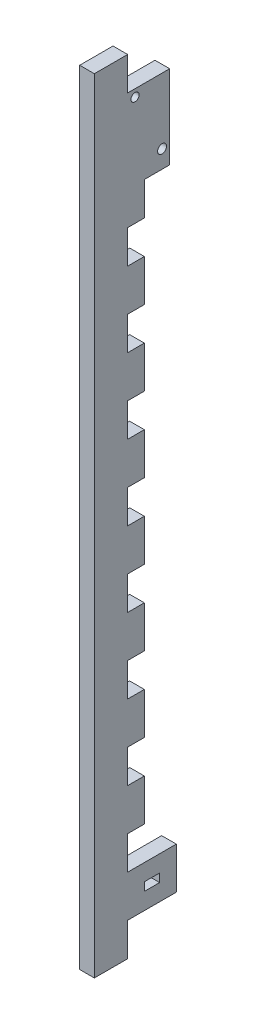
SolidWorks part; units mm, degrees
material "Acrylic (Medium-high impact)"
ref_plane "Front" through (0, 0, 0) normal (0, 0, 1) x (1, 0, 0)
ref_plane "Top" through (0, 0, 0) normal (0, 1, 0) x (1, 0, 0)
ref_plane "Right" through (0, 0, 0) normal (1, 0, 0) x (0, 0, -1)
sketch "Sketch1" plane through (0, 0, 0) normal (1, 0, 0) x (0, 0, -1)
  line L0 (9.525, 120.65) -> (9.525, 107.95)
  line L1 (-9.525, 149.225) -> (9.525, 149.225)
  line L2 (-9.525, 149.225) -> (-9.525, -149.225)
  line L3 (-9.525, -149.225) -> (9.525, -149.225)
  line L4 (9.525, 149.225) -> (9.525, -149.225)
  line L17 (9.525, 149.225) -> (3.175, 149.225)
  line L22 (9.525, 149.225) -> (9.525, 136.525)
  line L27 (9.525, 136.525) -> (3.175, 136.525)
  line L32 (3.175, 149.225) -> (3.175, 136.525)
  line L37 (9.525, 120.65) -> (3.175, 120.65)
  line L42 (3.175, 120.65) -> (3.175, 107.95)
  line L47 (9.525, 107.95) -> (3.175, 107.95)
  line L52 (9.525, 92.075) -> (9.525, 79.375)
  line L57 (9.525, 92.075) -> (3.175, 92.075)
  line L62 (3.175, 92.075) -> (3.175, 79.375)
  line L67 (9.525, 79.375) -> (3.175, 79.375)
  line L68 (9.525, 63.5) -> (9.525, 50.8)
  line L72 (9.525, 63.5) -> (3.175, 63.5)
  line L73 (3.175, 63.5) -> (3.175, 50.8)
  line L78 (9.525, 50.8) -> (3.175, 50.8)
  line L79 (9.525, 34.925) -> (9.525, 22.225)
  line L80 (9.525, 34.925) -> (3.175, 34.925)
  line L81 (3.175, 34.925) -> (3.175, 22.225)
  line L82 (9.525, 22.225) -> (3.175, 22.225)
  line L83 (9.525, 6.35) -> (9.525, -6.35)
  line L84 (9.525, 6.35) -> (3.175, 6.35)
  line L85 (3.175, 6.35) -> (3.175, -6.35)
  line L86 (9.525, -6.35) -> (3.175, -6.35)
  line L87 (9.525, -22.225) -> (9.525, -34.925)
  line L88 (9.525, -22.225) -> (3.175, -22.225)
  line L89 (3.175, -22.225) -> (3.175, -34.925)
  line L90 (9.525, -34.925) -> (3.175, -34.925)
  line L91 (9.525, -50.8) -> (9.525, -63.5)
  line L92 (9.525, -50.8) -> (3.175, -50.8)
  line L93 (3.175, -50.8) -> (3.175, -63.5)
  line L94 (9.525, -63.5) -> (3.175, -63.5)
  line L95 (9.525, -79.375) -> (9.525, -92.075)
  line L96 (9.525, -79.375) -> (3.175, -79.375)
  line L97 (3.175, -79.375) -> (3.175, -92.075)
  line L98 (9.525, -92.075) -> (3.175, -92.075)
  line L99 (9.525, -107.95) -> (9.525, -120.65)
  line L100 (9.525, -107.95) -> (3.175, -107.95)
  line L101 (3.175, -107.95) -> (3.175, -120.65)
  line L102 (9.525, -120.65) -> (3.175, -120.65)
  line L103 (9.525, -136.525) -> (9.525, -149.225)
  line L104 (9.525, -136.525) -> (3.175, -136.525)
  line L105 (3.175, -136.525) -> (3.175, -149.225)
  line L106 (9.525, -149.225) -> (3.175, -149.225)
  point P4 (0, -149.225)
  point P6 (-9.525, 0)
  dimension "D1" = 19.05
  dimension "D2" = 298.45
  dimension "D3" = 12.7
  dimension "D4" = 6.35
  dimension "D5" = 11
extrude "Boss-Extrude1" add sketch "Sketch1" along normal blind 5.588 contours L4 L103 L91 L79 L1 L2 L3 region at (0, 0, 1.1739)
sketch "Sketch2" plane through (5.588, 0, 0) normal (1, 0, 0) x (0, 0, -1)
  line L5 (9.525, -136.525) -> (3.175, -136.525) construction
  line L6 (9.525, -120.65) -> (21.717, -120.65)
  line L7 (9.525, -120.65) -> (9.525, -136.525)
  line L8 (9.525, -136.525) -> (21.717, -136.525)
  line L9 (21.717, -120.65) -> (21.717, -136.525)
  line L10 (19.075, 136.525) -> (19.075, 104.775) construction
  line L11 (9.525, -127) -> (15.367, -127)
  line L12 (9.525, -127) -> (9.525, -130.175)
  line L13 (9.525, -130.175) -> (15.367, -130.175)
  line L14 (15.367, -127) -> (15.367, -130.175)
  line L19 (3.175, 136.525) -> (19.175, 136.525)
  line L20 (3.175, 136.525) -> (3.175, 104.775)
  line L21 (3.175, 104.775) -> (19.175, 104.775)
  line L22 (19.175, 136.525) -> (19.175, 104.775)
  circle A1 centre (5.975, 133.725) radius 1.55
  circle A2 centre (16.275, 111.525) radius 1.7
  point P22 (15.367, -128.5875)
  point P27 (21.717, -128.5875)
  line M21 (9.525, -136.525) -> (9.525, -120.65)
  line M55 (3.175, 107.95) -> (3.175, 120.65)
  line M56 (3.175, 120.65) -> (9.525, 120.65)
  line M57 (9.525, 120.65) -> (9.525, 136.525)
  line M58 (9.525, 136.525) -> (3.175, 136.525)
  dimension "D1" = 12.192
  dimension "D2" = 16
  dimension "D6" = 3.1
  dimension "D7" = 3.4
  dimension "D3" = 3.175
  dimension "D4" = 5.842
  dimension "D5" = 31.75
  dimension "D8" = 22.2
  dimension "D9" = 10.3
  dimension "D10" = 15.9
  dimension "D11" = 2.8
  dimension "D12" = 2.8
extrude "Boss-Extrude2" add sketch "Sketch2" against normal up to surface (5.588 mm away) contours L10 L19 L21 A2 M57 M56 M55 | L20 A1 M58 M56 M57 | L19 L10 L21 L22 | L11 L14 L13 L8 L9 L6 L7 M21 region at (5.588, -128.5875, -15.9575) region at (5.588, 120.65, -19.125) region at (5.588, 118.8338, -12.2254) region at (5.588, 128.1717, -6.3803) up to face at (0, 0, -5.4841)
extrude "Cut-Extrude1" cut sketch "Sketch2<4>" against normal through all contours A1
sketch "Sketch2<4>" plane through (5.588, 0, 0) normal (1, 0, 0) x (0, 0, -1) same geometry as "Sketch2"
